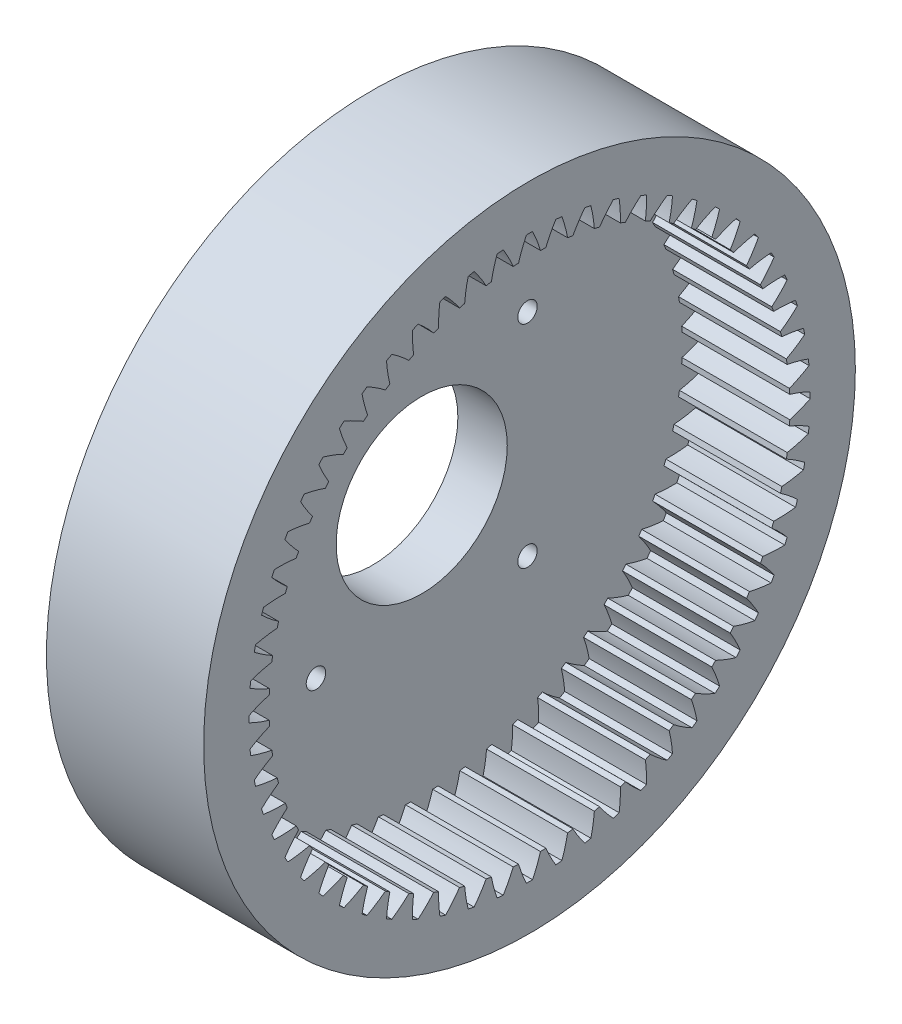
SolidWorks part; units mm, degrees
ref_plane "Plane1" through (0, 0, 0) normal (0, 0, 1) x (1, 0, 0)
ref_plane "Plane2" through (0, 0, 0) normal (0, 1, 0) x (1, 0, 0)
ref_plane "Plane3" through (0, 0, 0) normal (1, 0, 0) x (0, 0, -1)
sketch "HoldingSke" plane through (0, 0, 0) normal (0, 1, 0) x (1, 0, 0)
  line L0 (0, 0) -> (0.5, -0.866)
  line L1 (-15, 0) -> (100, 0) construction
  line L2 (0, 0) -> (-2.1039, 2.3779)
  line L3 (0, 0) -> (-11.863, 4.5341)
  line L4 (0, 0) -> (4.318, 7.479)
  line L5 (0, 0) -> (-23.7986, -8.8762)
  line L6 (0, 0) -> (-10.5278, -7.1032)
  line L7 (-2.1039, 2.3779) -> (3.3635, 27.1825)
  line L8 (-76.2, 3.3779) -> (-54.61, 3.3779)
  line L9 (-71.009, 38.7566) -> (-53.1078, 45.2721)
  line L10 (-76.2, 71.12) -> (104.1128, 71.12)
  line L11 (0, 0) -> (-12, 0)
  line L12 (-76.2, 101.6) -> (-76.162, 101.6)
  line L13 (24.9733, 27.94) -> (52.9518, 28.4284)
  line L14 (24.9733, 27.94) -> (24.9743, 27.94)
  line L15 (24.9733, 27.94) -> (100.4006, 29.5858)
  circle A0 centre (0, 0) radius 12.5
  circle A1 centre (0, 0) radius 12.7
  circle A2 centre (0, 0) radius 12.7
  dimension "MHD" = 25.4
  dimension "Hub_dia" = 25.4
  dimension "Diameter" = 25
  dimension "Num_teeth" = 60
  dimension "Pitch" = 1
  dimension "Overall_len" = 25.4
  dimension "Show_teeth" = 60
  dimension "Thickness" = 12.7
  dimension "OAL" = 25.4001
  dimension "T_dim" = 21.59
  dimension "Ap" = 20
  dimension "H" = 19.05
  dimension "Pitch_radius" = 180.3128
  dimension "Width" = 12
  dimension "Backlash" = 0.038
  dimension "Addendum_fac" = 1
  dimension "Dedendum_fac" = 1.25
  dimension "Clearance_fac" = 0.25
  dimension "Dedendum_add" = 0.001
  dimension "Module" = 1
sketch "BasProSke" plane through (0, 0, 0) normal (0, 1, 0) x (1, 0, 0)
  line L0 (-10, 0) -> (60, 0) construction
  line L1 (0, 29) -> (0, 31.2764)
  line L2 (0, 29) -> (12, 29)
  line L3 (12, 29) -> (12, 31.2764)
  line L4 (12, 31.2764) -> (0, 31.2764)
  dimension "Thickness" = 12
  dimension "Diameter" = 62.5528
  dimension "Inside_diameter" = 58
revolve "Base-Revolve" add sketch "BasProSke" angle 360 about L0
sketch "TooCutSke" plane through (0, 0, 0) normal (1, 0, 0) x (0, 0, -1)
  line L3 (0.8803, 29.9871) -> (0.8803, 53.6633) construction
  line L4 (0, 0) -> (0, 59.563) construction
  line L5 (0, 0) -> (-3.576, 68.2339) construction
  line L6 (-13.1633, 24.7167) -> (36.4631, 27.3175) construction
  circle A0 centre (0, 0) radius 30 construction
  circle A1 centre (0, 0) radius 31.251 construction
  circle A2 centre (0, 0) radius 25.3717 construction
  circle A3 centre (0, 0) radius 28.9746 construction
  arc A4 (1.2274, 28.9486) -> (0.3395, 31.2492) centre (-13.1633, 24.7167) ccw
  arc A5 (1.2274, 28.9486) -> (-1.2274, 28.9486) centre (0, 0) ccw
  arc A6 (0.3395, 31.2492) -> (-0.3395, 31.2492) centre (0, 0) ccw
  arc A7 (-0.3395, 31.2492) -> (-1.2274, 28.9486) centre (13.1633, 24.7167) ccw
  dimension "Pitch_dia" = 60
  dimension "Base_dia" = 50.7434
  dimension "Root_dia" = 62.502
  dimension "Overcut_dia" = 57.9492
  dimension "Flank_rad" = 15
  dimension "Half_ang" = 3
  dimension "Half_CT" = 0.8803
extrude "ToothCut" cut sketch "TooCutSke" along normal through all
fillet "Breaks" [suppressed] radius 0.1
fillet "RootFillets" [suppressed] radius 0.251
pattern_circular "TeethCuts" count 60 every 6 about axis through (-10, 0, 0) along (1, 0, 0) of "RootFillets", "Breaks", "ToothCut"
scale "Scale1" scale about centroid uniform scaling yes scale factor 2
sketch "Sketch1" plane through (18, 0, 0) normal (1, 0, 0) x (0, 0, -1)
  circle A0 centre (0, 0) radius 62.5528
extrude "Extrude-Thin1" add sketch "Sketch1" against normal blind 35 separate body thin thin type one direction wall 10
sketch "Sketch2" plane through (-6, 0, 0) normal (-1, 0, 0) x (0, 0, 1)
  circle A0 centre (0, 0) radius 62.5528
extrude "Boss-Extrude1" add sketch "Sketch2" along normal blind 11
sketch "Sketch3" plane through (-6, 0, 0) normal (1, 0, 0) x (0, 0, -1)
  circle A0 centre (0, 0) radius 19.05
  dimension "D1" = 38.1
extrude "Cut-Extrude1" cut sketch "Sketch3" against normal through all
sketch "Sketch5" plane through (-6, 0, 0) normal (1, 0, 0) x (0, 0, -1)
  line L6 (22.0191, 22.0191) -> (-22.0191, -22.0191) construction
  circle A0 centre (-23.55, 23.55) radius 2.165
  circle A1 centre (-23.55, -23.55) radius 2.165
  circle A2 centre (23.55, 23.55) radius 2.165
  circle A3 centre (23.55, -23.55) radius 2.165
  point P0 (0, 0)
  dimension "D1" = 47.1
  dimension "D2" = 47.1
extrude "Cut-Extrude2" cut sketch "Sketch5" against normal through all
equation "' \"Module@HoldingSke\" = 6.35"
equation "' \"Num_teeth@HoldingSke\" = 24"
equation "' \"Ap@HoldingSke\" =  14.5"
equation "' \"Ap@HoldingSke\" = 14.5"
equation "' \"Width@HoldingSke\" = 12"
equation "' \"Diameter@HoldingSke\" = 8 * 25.4"
equation "' \"Show_teeth@HoldingSke\" = 100"
equation "' \"Backlash@HoldingSke\" = 0.009 * 25.4"
equation "' \"Addendum_fac@HoldingSke\" = 1.0"
equation "' \"Dedendum_fac@HoldingSke\" = 1.25"
equation "' \"Dedendum_add@HoldingSke\" = 0.00005 * 25.4"
equation "' \"Clearance_fac@HoldingSke\" = 0.25"
equation "\"Pitch@HoldingSke\" = 1 / \"Module@HoldingSke\" "
equation "\"Overcut_dia@TooCutSke\" = (\"Num_teeth@HoldingSke\" - 2 * \"Addendum_fac@HoldingSke\") / \"Pitch@HoldingSke\" - 0.002 * 25.4"
equation "\"Pitch_dia@TooCutSke\" = \"Num_teeth@HoldingSke\" / \"Pitch@HoldingSke\""
equation "\"Base_dia@TooCutSke\" = \"Num_teeth@HoldingSke\" / \"Pitch@HoldingSke\" * cos((\"Ap@HoldingSke\"  * 3.14159265 / 180)) * 0.90"
equation "\"Root_dia@TooCutSke\" = \"Num_teeth@HoldingSke\"  / \"Pitch@HoldingSke\" + 2 *  \"Dedendum_fac@HoldingSke\"/ \"Pitch@HoldingSke\" + \"Dedendum_add@HoldingSke\" * 2"
equation "\"Half_ang@TooCutSke\" = 180 / \"Num_teeth@HoldingSke\""
equation "\"Half_CT@TooCutSke\" = \"Num_teeth@HoldingSke\" / \"Pitch@HoldingSke\" * sin((3.14159265 / 2 / \"Num_teeth@HoldingSke\")) / 2 + 10 * \"Backlash@HoldingSke\" / 4"
equation "\"Flank_rad@TooCutSke\" = \"Num_teeth@HoldingSke\" / \"Pitch@HoldingSke\" / 4"
equation "\"Radius@RootFillets\"= \"Clearance_fac@HoldingSke\" / \"Pitch@HoldingSke\" + \"Dedendum_add@HoldingSke\""
equation "\"Break_rad@Breaks\" = 0.02 / \"Pitch@HoldingSke\" * 5"
equation "\"Num_teeth@TeethCuts\" = int( \"Show_teeth@HoldingSke\" ) + 1"
equation "\"Num_teeth@TeethCuts\" = ((sgn( \"Num_teeth@TeethCuts\" - \"Num_teeth@HoldingSke\" )-1)*( \"Num_teeth@TeethCuts\" - \"Num_teeth@HoldingSke\" ))/-2+ \"Num_teeth@HoldingSke\""
equation "\"Num_teeth@TeethCuts\" = ((sgn( \"Num_teeth@TeethCuts\" - 2.0)+1)*( \"Num_teeth@TeethCuts\" - 2.0))/2 +2.0"
equation "\"Angle@TeethCuts\" = 360.0 / \"Num_teeth@HoldingSke\""
equation "\"Diameter@BasProSke\" = \"Num_teeth@HoldingSke\"  / \"Pitch@HoldingSke\" + 2 *  \"Dedendum_fac@HoldingSke\"/ \"Pitch@HoldingSke\" + \"Dedendum_add@HoldingSke\" * 2 + 0.002 * 25.4"
equation "\"Diameter@BasProSke\" = ((sgn( \"Diameter@BasProSke\"  - \"Diameter@HoldingSke\" )+1)*( \"Diameter@BasProSke\"  - \"Diameter@HoldingSke\" ))/2 + \"Diameter@HoldingSke\""
equation "\"Inside_diameter@BasProSke\" =  (\"Num_teeth@HoldingSke\" - 2 * \"Addendum_fac@HoldingSke\") / \"Pitch@HoldingSke\" "
equation "\"Thickness@BasProSke\"  = \"Width@HoldingSke\""
